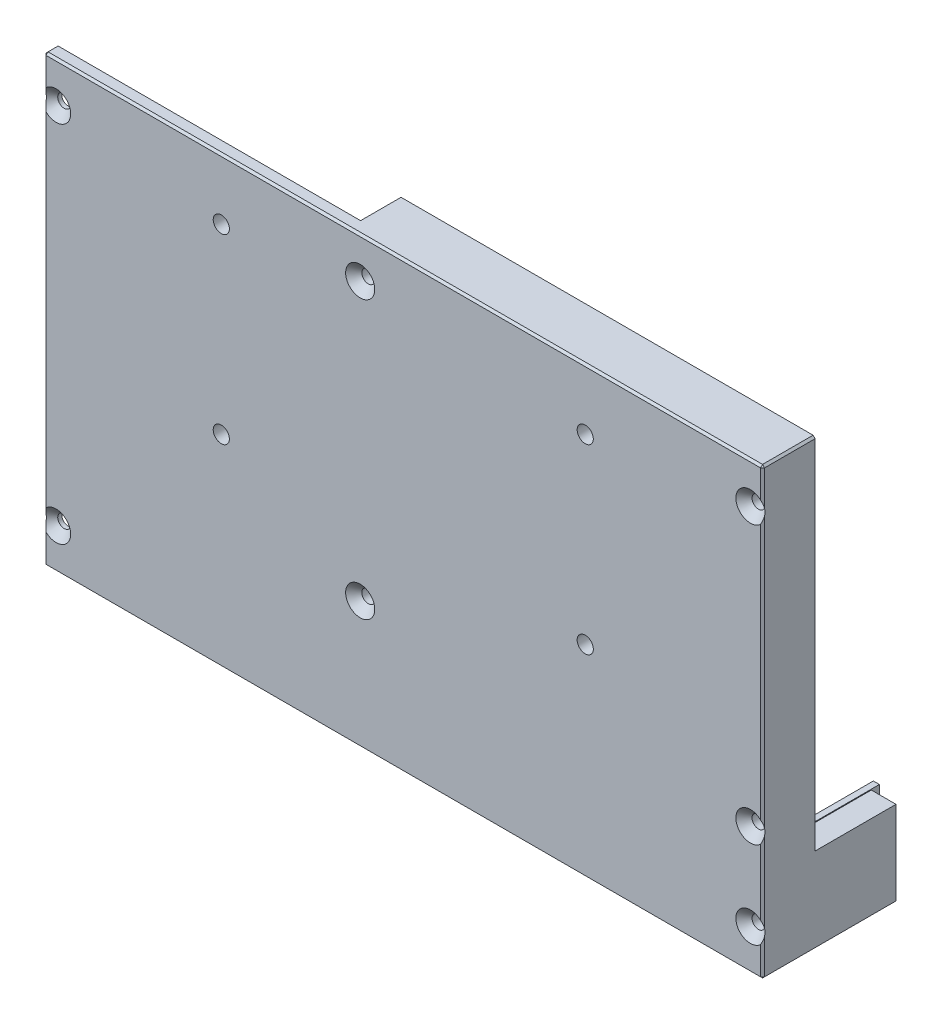
SolidWorks part; units mm, degrees
ref_plane "Plan de face" through (0, 0, 0) normal (0, 0, 1) x (1, 0, 0)
ref_plane "Plan de dessus" through (0, 0, 0) normal (0, 1, 0) x (1, 0, 0)
ref_plane "Plan de droite" through (0, 0, 0) normal (1, 0, 0) x (0, 0, -1)
sketch "Esquisse1" plane through (0, 0, 0) normal (0, 0, 1) x (1, 0, 0)
  line L1 (0, 0) -> (177.7, 0)
  line L2 (0, 0) -> (0, 110)
  line L3 (0, 110) -> (177.7, 110)
  line L4 (177.7, 0) -> (177.7, 110)
  dimension "D1" = 177.7
  dimension "D2" = 110
extrude "Boss.-Extru.1" add sketch "Esquisse1" along normal blind 3
sketch "Esquisse2" plane through (0, 0, 0) normal (0, 0, -1) x (-1, 0, 0)
  line L1 (-177.7, 110) -> (-75.1, 110)
  line L2 (-177.7, 110) -> (-177.7, 21.4)
  line L3 (-177.7, 21.4) -> (-75.1, 21.4)
  line L4 (-75.1, 110) -> (-75.1, 21.4)
  dimension "D1" = 102.6
  dimension "D2" = 88.6
extrude "Boss.-Extru.2" add sketch "Esquisse2" along normal blind 10
sketch "Esquisse3" plane through (0, 0, 0) normal (0, 0, -1) x (-1, 0, 0)
  line L0 (-177.7, 21.4) -> (-171.6, 21.4)
  line L1 (-171.6, 21.4) -> (-171.6, 3.2)
  line L2 (-171.6, 3.2) -> (-16.2, 3.2)
  line L3 (-16.2, 3.2) -> (-16.2, 0)
  line L4 (0, 0) -> (-177.7, 0) construction
  line L5 (-16.2, 0) -> (-177.7, 0)
  line L6 (-177.7, 0) -> (-177.7, 21.4)
  line L7 (0, 110) -> (0, 0) construction
  dimension "D1" = 6.1
  dimension "D2" = 3.2
  dimension "D3" = 16.2
extrude "Boss.-Extru.3" add sketch "Esquisse3" along normal blind 30
sketch "Esquisse4" plane through (0, 21.4, 0) normal (0, 1, 0) x (1, 0, 0)
  line L1 (177.7, 30) -> (171.6, 30)
  line L2 (177.7, 30) -> (177.7, 10)
  line L3 (177.7, 10) -> (171.6, 10)
  line L4 (171.6, 30) -> (171.6, 10)
extrude "Enlèv. mat.-Extru.1" cut sketch "Esquisse4" against normal blind 0.2
sketch "Esquisse5" plane through (75.1, 0, 0) normal (-1, 0, 0) x (0, 0, 1)
  line L0 (0, 21.4) -> (0, 110) construction
  line L1 (-10, 110) -> (0, 110)
  line L2 (-10, 110) -> (-10, 106.8)
  line L3 (-10, 106.8) -> (0, 106.8)
  line L4 (0, 110) -> (0, 106.8)
  dimension "D1" = 3.2
extrude "Enlèv. mat.-Extru.2" cut sketch "Esquisse5" against normal blind 0.2
sketch "Esquisse6" plane through (0, 0, 0) normal (0, 0, -1) x (-1, 0, 0)
  line L0 (-75.1, 106.8) -> (-6.1, 106.8)
  line L1 (-6.1, 106.8) -> (-6.1, 3.2)
  line L2 (-171.6, 3.2) -> (-6.1, 3.2)
  line L3 (-171.6, 3.2) -> (-171.6, 21.4)
  line L4 (0, 110) -> (0, 0) construction
  line L6 (-75.1, 21.4) -> (-75.1, 106.8) construction
  line L7 (-73.6, 105.3) -> (-7.6, 105.3)
  line L8 (-7.6, 105.3) -> (-7.6, 4.7)
  line L9 (-7.6, 4.7) -> (-170.1, 4.7)
  line L10 (-170.1, 4.7) -> (-170.1, 19.9)
  line L13 (-170.1, 4.7) -> (-170.1, 3.2) construction
  line L14 (-7.6, 4.7) -> (-6.1, 4.7) construction
  line L17 (-75.1, 106.8) -> (-75.1, 21.4)
  line L18 (-75.1, 21.4) -> (-171.6, 21.4)
  line L19 (-170.1, 19.9) -> (-73.6, 19.9)
  line L20 (-73.6, 19.9) -> (-73.6, 105.3)
  line L21 (-170.1, 19.9) -> (-171.6, 19.9) construction
  line L22 (-75.1, 21.4) -> (-75.1, 19.9) construction
  line L23 (-73.6, 105.3) -> (-73.6, 106.8) construction
  line L24 (-75.1, 21.4) -> (-73.6, 21.4) construction
  dimension "D1" = 6.1
  dimension "D2" = 1.5
extrude "Boss.-Extru.4" add sketch "Esquisse6" along normal blind 2
sketch "Esquisse7" plane through (0, 0, -2) normal (0, 0, -1) x (-1, 0, 0)
  line L12 (-75.1, 106.8) -> (-73.6, 106.8)
  line L13 (-75.3, 106.8) -> (-6.1, 106.8) construction
  line L14 (-73.6, 106.8) -> (-73.6, 19.4)
  line L15 (-73.6, 19.4) -> (-171.6, 19.4)
  line L16 (-171.6, 3.2) -> (-171.6, 21.2) construction
  line L17 (-171.6, 19.4) -> (-171.6, 21.4)
  line L18 (-171.6, 21.4) -> (-75.1, 21.4)
  line L19 (-75.1, 21.4) -> (-75.1, 106.8)
  line L20 (-6.1, 106.8) -> (-75.1, 106.8) construction
  line L21 (-73.6, 105.3) -> (-73.6, 19.9) construction
  dimension "D1" = 2
ref_plane "Plan1" through (0, 0, -12) normal (0, 0, -1) x (-1, 0, 0)
extrude "Boss.-Extru.5" add sketch "Esquisse7" along normal up to surface (10 mm away) up to plane "Plan1"
sketch "Esquisse8" plane through (0, 0, -2) normal (0, 0, -1) x (-1, 0, 0)
  line L0 (-14.2, 3.2) -> (-14.2, 4.7)
  line L1 (-16.2, 3.2) -> (-6.1, 3.2) construction
  line L2 (-7.6, 4.7) -> (-170.1, 4.7) construction
  line L3 (-14.2, 4.7) -> (-170.1, 4.7)
  line L4 (-170.1, 4.7) -> (-170.1, 21.4)
  line L6 (-170.1, 21.4) -> (-171.6, 21.4)
  line L8 (-171.6, 21.4) -> (-171.6, 3.2)
  line L9 (-171.6, 3.2) -> (-14.2, 3.2)
  line L10 (-16.2, 0) -> (-16.2, 3.2) construction
  line L13 (-171.6, 21.4) -> (-75.1, 21.4) construction
  line L14 (-75.1, 21.4) -> (-171.6, 21.4) construction
  dimension "D1" = 2
ref_plane "Plan2" through (0, 0, -32) normal (0, 0, -1) x (-1, 0, 0)
extrude "Boss.-Extru.6" add sketch "Esquisse8" along normal up to surface (30 mm away) up to plane "Plan2"
sketch "Esquisse9" plane through (0, 0, 3) normal (0, 0, 1) x (1, 0, 0)
  line L0 (3, 110) -> (3, 100) construction
  line L1 (177.7, 110) -> (0, 110) construction
  line L2 (3, 100) -> (3, 10) construction
  line L3 (3, 10) -> (3, 0) construction
  line L4 (0, 0) -> (177.7, 0) construction
  line L5 (174.7, 110) -> (174.7, 100) construction
  line L6 (174.7, 100) -> (174.7, 10) construction
  line L7 (174.7, 10) -> (174.7, 0) construction
  line L8 (0, 110) -> (0, 0) construction
  line L9 (177.7, 0) -> (177.7, 110) construction
  line L11 (174.7, 100) -> (78.2, 100) construction
  line L12 (174.7, 100) -> (174.7, 31.5) construction
  line L13 (174.7, 31.5) -> (78.2, 31.5) construction
  line L14 (78.2, 100) -> (78.2, 31.5) construction
  circle A0 centre (3, 100) radius 1.6
  circle A1 centre (3, 10) radius 1.6
  circle A2 centre (174.7, 100) radius 1.6
  circle A3 centre (174.7, 10) radius 1.6
  circle A4 centre (78.2, 100) radius 1.6
  circle A5 centre (78.2, 31.5) radius 1.6
  circle A6 centre (174.7, 31.5) radius 1.6
  dimension "D4" = 3.2
  dimension "D1" = 3
  dimension "D2" = 3
  dimension "D3" = 10
  dimension "D5" = 96.5
  dimension "D6" = 68.5
extrude "Enlèv. mat.-Extru.3" cut sketch "Esquisse9" against normal through all
chamfer "Chanfrein1" distance 2 angle 45 7 edges at (4.6, 10, 3) (79.8, 31.5, 3) (176.3, 10, 3) (176.3, 31.5, 3) (176.3, 100, 3) (79.8, 100, 3) (4.6, 100, 3)
chamfer "Chanfrein2" distance 0.5 angle 45 13 edges at (177.7, 65.75, 3) (177.7, 20.75, 3) (0, 4.005, 3) (177.7, 4.005, 3) (88.85, 0, 3) (0, 55, 3) (177.7, 105.995, 3) (0, 105.995, 3) (88.85, 110, 3) (0, 0, 1.5) (177.7, 0, -13.5) (0, 110, 1.5) (177.7, 110, -3.5)
sketch "Esquisse10" plane through (0, 0, 3) normal (0, 0, 1) x (1, 0, 0)
  line L0 (88.85, 109.5) -> (88.85, 95) construction
  line L1 (43.85, 50) -> (133.85, 50) construction
  line L2 (43.85, 50) -> (43.85, 95) construction
  line L3 (43.85, 95) -> (133.85, 95) construction
  line L4 (133.85, 50) -> (133.85, 95) construction
  line L5 (43.85, 50) -> (133.85, 95) construction
  line L6 (43.85, 95) -> (133.85, 50) construction
  line L7 (177.2, 109.5) -> (0.5, 109.5) construction
  line L8 (0.5, 110) -> (177.2, 110) construction
  circle A0 centre (43.85, 95) radius 2
  circle A1 centre (43.85, 50) radius 2
  circle A2 centre (133.85, 95) radius 2
  circle A3 centre (133.85, 50) radius 2
  point P0 (88.85, 72.5)
  dimension "D2" = 4
  dimension "D1" = 90
  dimension "D3" = 45
  dimension "D4" = 15
extrude "Enlèv. mat.-Extru.4" cut sketch "Esquisse10" against normal blind 5
sketch "Esquisse11" plane through (0, 0, 3) normal (0, 0, 1) x (1, 0, 0)
  circle A0 centre (43.85, 95) radius 2
  circle A1 centre (43.85, 95) radius 4
  circle A2 centre (43.85, 50) radius 4
  circle A3 centre (43.85, 50) radius 2
  circle A4 centre (133.85, 95) radius 2
  circle A5 centre (133.85, 95) radius 4
  circle A6 centre (133.85, 50) radius 2
  circle A7 centre (133.85, 50) radius 4
  circle A8 centre (43.85, 50) radius 2 construction
  dimension "D1" = 2
extrude "Boss.-Extru.7" add sketch "Esquisse11" against normal blind 5
sketch "Esquisse13" plane through (0, 0, -32) normal (0, 0, -1) x (-1, 0, 0)
  line L0 (-177.2, 0) -> (-16.2, 0) construction
  line L1 (-21.2, 4.7) -> (-39.2, 4.7)
  line L2 (-21.2, 4.7) -> (-21.2, 0)
  line L3 (-21.2, 0) -> (-39.2, 0)
  line L4 (-39.2, 4.7) -> (-39.2, 0)
  line L6 (-170.1, 4.7) -> (-7.6, 4.7) construction
  line L7 (-67.2, 4.7) -> (-49.2, 4.7)
  line L8 (-67.2, 4.7) -> (-67.2, 0)
  line L9 (-67.2, 0) -> (-49.2, 0)
  line L10 (-49.2, 4.7) -> (-49.2, 0)
  line L11 (-16.2, 0) -> (-16.2, 3.2) construction
  dimension "D1" = 5
  dimension "D2" = 18
  dimension "D3" = 10
  dimension "D4" = 18
extrude "Enlèv. mat.-Extru.5" cut sketch "Esquisse13" against normal blind 7
sketch "Esquisse14" plane through (0, 0, -2) normal (0, 0, 1) x (1, 0, 0)
  line L1 (73.6, 19.9) -> (170.1, 19.9)
  line L2 (73.6, 19.9) -> (73.6, 19.4)
  line L3 (73.6, 19.4) -> (170.1, 19.4)
  line L4 (170.1, 19.9) -> (170.1, 19.4)
extrude "Boss.-Extru.8" add sketch "Esquisse14" along normal up to surface (2 mm away) up to face at (39.85, 50, 0)
